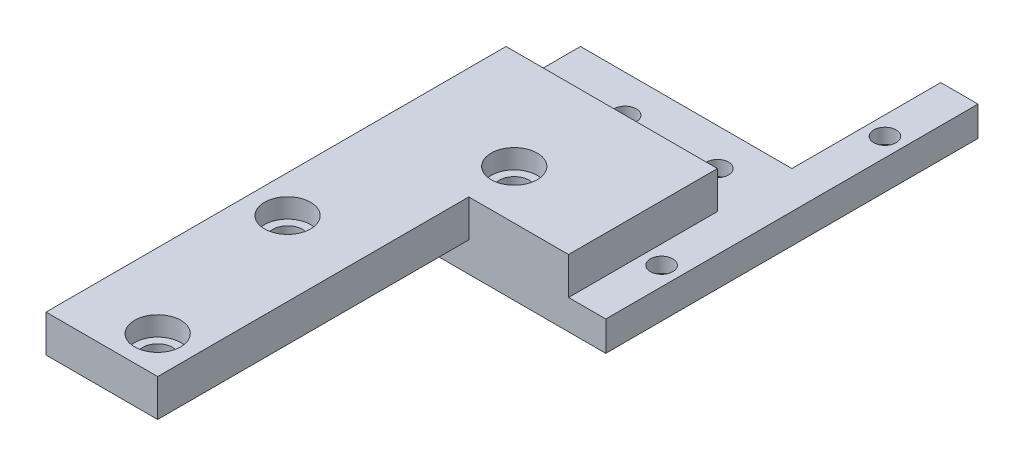
SolidWorks part; units mm, degrees
other "标注1"
sketch "草图3" plane through (0, 5, 29.5) normal (-0.6417, 0.7662, 0.0339) x (0.7661, 0.6384, 0.0747)
ref_plane "前视基准面" through (0, 0, 0) normal (0, 0, 1) x (1, 0, 0)
ref_plane "上视基准面" through (0, 0, 0) normal (0, 1, 0) x (1, 0, 0)
ref_plane "右视基准面" through (0, 0, 0) normal (1, 0, 0) x (0, 0, -1)
other "Configuration Table"
sketch "草图4" plane through (0, 0, 0) normal (0, 1, 0) x (1, 0, 0)
  line L1 (0, 0) -> (-28.4, 0)
  line L2 (0, 0) -> (0, -61.7963)
  line L3 (0, -61.7963) -> (-28.4, -61.7963)
  line L4 (-28.4, 0) -> (-28.4, -61.7963)
  line L9 (0, -61.7963) -> (-13.4, -61.7963)
  line L10 (0, -61.7963) -> (0, -20)
  line L11 (0, -20) -> (-13.4, -20)
  line L12 (-13.4, -61.7963) -> (-13.4, -20)
  circle A0 centre (-13.9, -13.4) radius 3.1
  circle A1 centre (-23.4, -34.3464) radius 3.1
  circle A2 centre (-18.4, -56.7963) radius 3.1
  circle A3 centre (-13.9, -13.4) radius 2
  circle A4 centre (-23.4, -34.3464) radius 2
  circle A5 centre (-18.4, -56.7963) radius 2
  dimension "D1" = 4
  dimension "D4" = 6.2
  dimension "D2" = 5
  dimension "D3" = 5
  dimension "D5" = 5
extrude "凸台-拉伸1" add sketch "草图4" along normal blind 5 contours L1 L4 L3 L2
extrude "切除-拉伸1" cut sketch "草图4<4>" against normal blind 2.6 from surface contours A0 | A1 | A2 starting at face at (-14.2, 5, 30.8982)
sketch "草图4<4>" plane through (0, 0, 0) normal (0, 1, 0) x (1, 0, 0) same geometry as "草图4"
extrude "切除-拉伸2" cut sketch "草图4<5>" against normal through all from surface contours A3 | A4 | A5 starting at face at (-13.9, 5, 10.3)
sketch "草图4<5>" plane through (0, 0, 0) normal (0, 1, 0) x (1, 0, 0) same geometry as "草图4"
extrude "切除-拉伸3" cut sketch "草图4<6>" along normal through all contours L12 L3 L2 L11 region at (-6.7, 0, 40.8982)
sketch "草图4<6>" plane through (0, 0, 0) normal (0, 1, 0) x (1, 0, 0) same geometry as "草图4"
sketch "草图5" plane through (0, 0, 0) normal (0, -1, 0) x (1, 0, 0)
  line L1 (5, 20) -> (-28.4, 20)
  line L2 (5, 20) -> (5, -10)
  line L3 (5, -10) -> (-28.4, -10)
  line L4 (-28.4, 20) -> (-28.4, -10)
  line L5 (5, -10) -> (0, -10)
  line L6 (5, -10) -> (5, -30)
  line L7 (5, -30) -> (0, -30)
  line L8 (0, -10) -> (0, -30)
  circle A0 centre (-17.4, -5) radius 1.5
  circle A1 centre (-5, -5) radius 1.5
  circle A2 centre (2.5, 10) radius 1.5
  circle A3 centre (2.5, -20) radius 1.5
  circle A14 centre (-17.4, -5) radius 2.25
  circle A15 centre (-5, -5) radius 2.25
  circle A16 centre (2.5, 10) radius 2.25
  circle A17 centre (2.5, -20) radius 2.25
  dimension "D3" = 3
  dimension "D4" = 4.5
  dimension "D1" = 30
  dimension "D2" = 33.4
extrude "凸台-拉伸2" add sketch "草图5" along normal blind 4 contours L2 L1 L4 L3 | L5 L8 L7 L6
extrude "切除-拉伸5" cut sketch "草图5<3>" along normal through all contours A0 | A1 | A3 | A2
sketch "草图5<3>" plane through (0, 0, 0) normal (0, -1, 0) x (1, 0, 0) same geometry as "草图5"
extrude "切除-拉伸7" cut sketch "草图5<4>" against normal blind 2 from surface contours A16 | A15 | A14 | A17 starting at face at (-17.4, -4, -6.5)
sketch "草图5<4>" plane through (0, 0, 0) normal (0, -1, 0) x (1, 0, 0) same geometry as "草图5"
